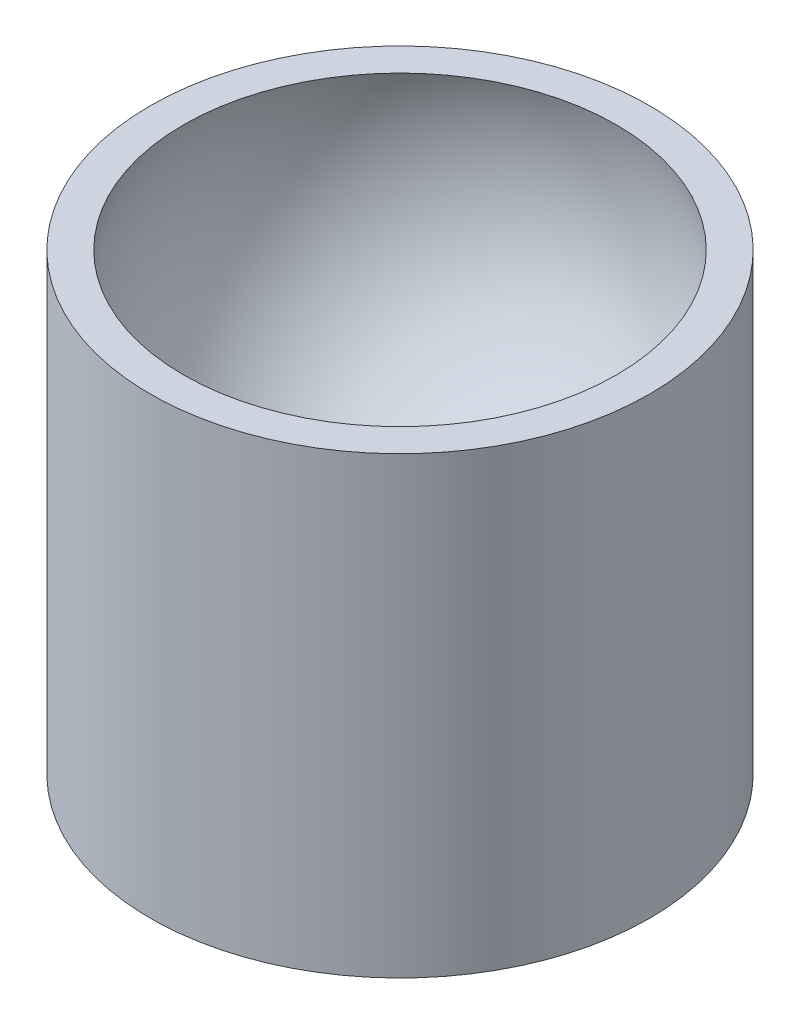
SolidWorks part; units mm, degrees
ref_plane "前视基准面" through (0, 0, 0) normal (0, 0, 1) x (1, 0, 0)
ref_plane "上视基准面" through (0, 0, 0) normal (0, 1, 0) x (1, 0, 0)
ref_plane "右视基准面" through (0, 0, 0) normal (1, 0, 0) x (0, 0, -1)
sketch "草图1" plane through (0, 0, 0) normal (0, 0, 1) x (1, 0, 0)
  line L0 (0, 0) -> (0, 6.614) construction
  line L1 (0, 6.614) -> (7.5003, 6.614) construction
  line L2 (7.5003, 6.614) -> (-7.5003, 6.614) construction
  line L3 (0, 0) -> (0, 3) construction
  line L6 (11, 3) -> (11, -17)
  line L7 (0, -17) -> (11, -17)
  line L8 (9.5394, 3) -> (11, 3)
  line L9 (0, -17) -> (0, -10)
  arc A0 (0, -10) -> (9.5394, 3) centre (0, 0) ccw
  point P9 (0, 3)
  dimension "D1" = 20
  dimension "D2" = 6.614
  dimension "D3" = 3
  dimension "D4" = 11
  dimension "D6" = 20
sketch "草图2" plane through (0, 0, 0) normal (0, 1, 0) x (1, 0, 0)
  circle A0 centre (0, 0) radius 11
sweep "扫描1" add profiles "草图1" path "草图2"
sketch "草图3" plane through (0, -17, 0) normal (0, -1, 0) x (1, 0, 0)
  circle A0 centre (0, 0) radius 5
  dimension "D1" = 10
extrude "切除-拉伸1" cut sketch "草图3" against normal through all
